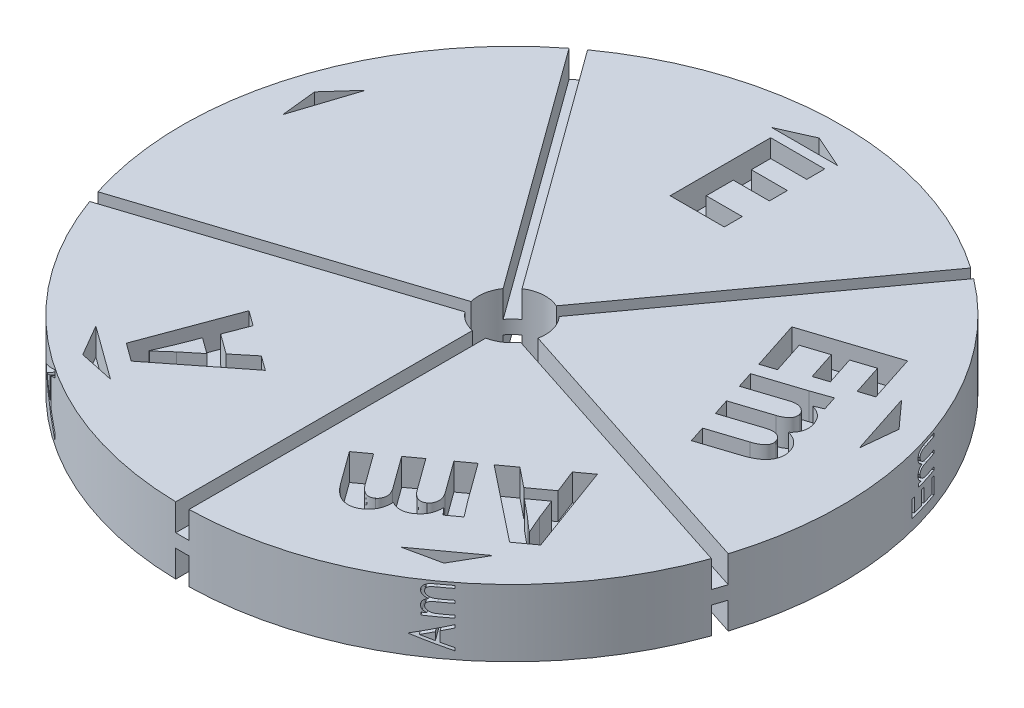
SolidWorks part; units mm, degrees
ref_plane "Front Plane" through (0, 0, 0) normal (0, 0, 1) x (1, 0, 0)
ref_plane "Top Plane" through (0, 0, 0) normal (0, 1, 0) x (1, 0, 0)
ref_plane "Right Plane" through (0, 0, 0) normal (1, 0, 0) x (0, 0, -1)
sketch "Sketch2" plane through (0, 0, 0) normal (0, 1, 0) x (1, 0, 0)
  circle A0 centre (0, 0) radius 3.175
  circle A1 centre (0, 0) radius 31.242
  dimension "D1" = 6.35
  dimension "D2" = 62.484
extrude "Boss-Extrude1" add sketch "Sketch2" along normal blind 6.35
sketch "Sketch3" plane through (0, 6.35, 0) normal (0, 1, 0) x (1, 0, 0)
  line L0 (0, 0) -> (0, 29.1218) construction
  line L1 (-8.7599, 17.3214) -> (8.7599, 17.3214) construction
  line L2 (0, 0) -> (27.6965, 8.9991) construction
  line L3 (13.7666, 13.6838) -> (19.1806, -2.9786) construction
  line L4 (0, 0) -> (17.1174, -23.56) construction
  line L5 (17.2682, -8.8643) -> (3.0943, -19.1622) construction
  line L6 (0, 0) -> (-17.1174, -23.56) construction
  line L7 (-3.0943, -19.1622) -> (-17.2682, -8.8643) construction
  line L8 (0, 0) -> (-27.6965, 8.9991) construction
  line L9 (-19.1806, -2.9786) -> (-13.7666, 13.6838) construction
  line L10 (-2.3202, 26.8464) -> (2.8087, 26.8464)
  line L11 (2.8087, 26.8464) -> (2.8087, 25.1368)
  line L12 (2.8087, 25.1368) -> (-0.6106, 25.1368)
  line L13 (-0.6106, 25.1368) -> (-0.6106, 23.305)
  line L14 (-0.6106, 23.305) -> (2.8087, 23.305)
  line L15 (2.8087, 23.305) -> (2.8087, 21.5954)
  line L16 (2.8087, 21.5954) -> (-0.6106, 21.5954)
  line L17 (-0.6106, 21.5954) -> (-0.6106, 19.031)
  line L18 (-0.6106, 19.031) -> (2.8087, 19.031)
  line L19 (2.8087, 19.031) -> (2.8087, 17.3214)
  line L20 (2.8087, 17.3214) -> (-2.3202, 17.3214)
  line L21 (-2.3202, 17.3214) -> (-2.3202, 26.8464)
  line L22 (16.0616, 11.1654) -> (18.3666, 11.9144)
  line L23 (18.3666, 11.9144) -> (19.2451, 9.2109)
  line L24 (19.2451, 9.2109) -> (20.5484, 9.6345)
  line L25 (20.5484, 9.6345) -> (19.6699, 12.338)
  line L26 (19.6699, 12.338) -> (21.6733, 12.989)
  line L27 (21.6733, 12.989) -> (22.6043, 10.1239)
  line L28 (22.6043, 10.1239) -> (23.9399, 10.5579)
  line L29 (23.9399, 10.5579) -> (22.4909, 15.0171)
  line L30 (22.4909, 15.0171) -> (14.208, 12.3255)
  line L31 (14.208, 12.3255) -> (15.7131, 7.694)
  line L32 (15.7131, 7.694) -> (17.0487, 8.128)
  line L33 (17.0487, 8.128) -> (16.0616, 11.1654)
  line L34 (21.7445, 6.7907) -> (21.7354, 6.8239)
  line L35 (21.7354, 6.8239) -> (22.5079, 7.1583)
  line L36 (22.5079, 7.1583) -> (22.0669, 8.5154)
  line L37 (20.281, 7.887) -> (16.0923, 6.5262)
  line L38 (16.0923, 6.5262) -> (16.5998, 4.9645)
  line L39 (16.5998, 4.9645) -> (20.2081, 6.137)
  line L40 (20.7301, 4.3062) -> (17.1878, 3.1549)
  line L41 (17.1878, 3.1549) -> (17.6954, 1.5932)
  line L42 (17.6954, 1.5932) -> (21.3359, 2.7762)
  line L43 (21.6757, 0.8859) -> (18.2834, -0.2164)
  line L44 (18.2834, -0.2164) -> (18.7909, -1.7781)
  line L45 (18.7909, -1.7781) -> (22.4315, -0.5951)
  line L46 (22.7262, 3.513) -> (22.7206, 3.5358)
  line L47 (20.2153, -17.4878) -> (17.0941, -8.9908)
  line L48 (17.0941, -8.9908) -> (15.7197, -9.9892)
  line L49 (15.7197, -9.9892) -> (16.5853, -12.202)
  line L50 (16.5853, -12.202) -> (14.6978, -13.5732)
  line L51 (14.6978, -13.5732) -> (12.8427, -12.0793)
  line L52 (12.8427, -12.0793) -> (11.4225, -13.111)
  line L53 (11.4225, -13.111) -> (18.5111, -18.7259)
  line L54 (18.5111, -18.7259) -> (20.2153, -17.4878)
  line L55 (18.6137, -16.9438) -> (18.5878, -16.9624)
  line L56 (17.2206, -15.7573) -> (15.6357, -14.4596)
  line L57 (15.6357, -14.4596) -> (17.1384, -13.368)
  line L58 (17.1384, -13.368) -> (17.8884, -15.2868)
  line L59 (12.5435, -19.0457) -> (12.5711, -19.0241)
  line L60 (12.5711, -19.0241) -> (13.1278, -19.6555)
  line L61 (13.1278, -19.6555) -> (14.2822, -18.8169)
  line L62 (13.1334, -17.3134) -> (10.5447, -13.7491)
  line L63 (10.5447, -13.7491) -> (9.2162, -14.7143)
  line L64 (9.2162, -14.7143) -> (11.446, -17.7837)
  line L65 (9.8656, -18.8474) -> (7.6769, -15.8325)
  line L66 (7.6769, -15.8325) -> (6.3483, -16.7977)
  line L67 (6.3483, -16.7977) -> (8.5981, -19.8946)
  line L68 (6.9042, -20.8025) -> (4.809, -17.9159)
  line L69 (4.809, -17.9159) -> (3.4805, -18.8811)
  line L70 (3.4805, -18.8811) -> (5.7303, -21.978)
  line L71 (9.7296, -20.991) -> (9.7482, -20.9768)
  line L72 (-14.2878, -21.7947) -> (-7.1717, -16.1998)
  line L73 (-7.1717, -16.1998) -> (-8.5461, -15.2014)
  line L74 (-8.5461, -15.2014) -> (-10.3829, -16.7086)
  line L75 (-10.3829, -16.7086) -> (-12.2704, -15.3374)
  line L76 (-12.2704, -15.3374) -> (-11.4231, -13.1114)
  line L77 (-11.4231, -13.1114) -> (-12.8433, -12.0796)
  line L78 (-12.8433, -12.0796) -> (-15.992, -20.5567)
  line L79 (-15.992, -20.5567) -> (-14.2878, -21.7947)
  line L80 (-14.2643, -20.1055) -> (-14.2912, -20.0845)
  line L81 (-13.5678, -18.4142) -> (-12.8235, -16.5034)
  line L82 (-12.8235, -16.5034) -> (-11.3208, -17.595)
  line L83 (-11.3208, -17.595) -> (-12.9138, -18.9014)
  line L84 (0, 29.1218) -> (-3.1045, 27.7361)
  line L85 (-3.1045, 27.7361) -> (3.1356, 27.7361)
  line L86 (3.1356, 27.7361) -> (0, 29.1218)
  line L87 (27.3475, 5.5888) -> (27.6965, 8.9991)
  line L88 (27.6965, 8.9991) -> (25.4192, 11.5235)
  line L89 (25.4192, 11.5235) -> (27.3475, 5.5888)
  line L90 (13.7661, -24.282) -> (17.1174, -23.56)
  line L91 (17.1174, -23.56) -> (18.8144, -20.6142)
  line L92 (18.8144, -20.6142) -> (13.7661, -24.282)
  line L93 (-18.8396, -20.5959) -> (-17.1174, -23.56)
  line L94 (-17.1174, -23.56) -> (-13.7913, -24.2637)
  line L95 (-13.7913, -24.2637) -> (-18.8396, -20.5959)
  line L96 (-25.4096, 11.553) -> (-27.6965, 8.9991)
  line L97 (-27.6965, 8.9991) -> (-27.3379, 5.6184)
  line L98 (-27.3379, 5.6184) -> (-25.4096, 11.553)
  spline S0 degree 3 poles (22.7206, 3.5358) (22.8505, 3.6417) (23.0222, 3.8266) (23.1833, 4.118) (23.2684, 4.3513) (23.3184, 4.5982) (23.3302, 4.9503) (23.2814, 5.2159) (23.2244, 5.3894) knots 0 0 0 0 0.245811 0.364788 0.485858 0.608329 0.732518 1 1 1 1
  spline S1 degree 3 poles (23.2244, 5.3894) (23.1882, 5.4952) (23.1257, 5.6475) (23.0256, 5.8372) (22.9463, 5.9655) (22.8634, 6.0844) (22.7724, 6.1913) (22.6762, 6.2882) (22.541, 6.4001) (22.3695, 6.5199) (22.0997, 6.676) (21.8871, 6.7566) (21.7445, 6.7907) knots 0 0 0 0 0.157381 0.231376 0.301838 0.36972 0.435229 0.499423 0.561679 0.682063 0.793713 1 1 1 1
  spline S2 degree 3 poles (22.0669, 8.5154) (21.7931, 8.4111) (21.2006, 8.1934) (20.6013, 7.9954) (20.281, 7.887) knots 0 0 0 0 0.464326 1 1 1 1
  spline S3 degree 3 poles (20.2081, 6.137) (20.3036, 6.1674) (20.4466, 6.1961) (20.6345, 6.221) (20.7652, 6.2239) (20.8891, 6.2159) (21.0065, 6.197) (21.1165, 6.1633) (21.2521, 6.1075) (21.4015, 6.0192) (21.5986, 5.8518) (21.6993, 5.6897) (21.7363, 5.573) knots 0 0 0 0 0.166013 0.241835 0.314414 0.382587 0.447893 0.511309 0.573122 0.691026 0.797762 1 1 1 1
  spline S4 degree 3 poles (21.7363, 5.573) (21.7588, 5.5001) (21.7791, 5.39) (21.7797, 5.2448) (21.7665, 5.1439) (21.7406, 5.0474) (21.6981, 4.9566) (21.6447, 4.8693) (21.5516, 4.7608) (21.4115, 4.6366) (21.1364, 4.4559) (20.8985, 4.359) (20.7301, 4.3062) knots 0 0 0 0 0.125369 0.182881 0.238167 0.292234 0.346525 0.40263 0.460044 0.580943 0.709299 1 1 1 1
  spline S5 degree 3 poles (21.3359, 2.7762) (21.4338, 2.8056) (21.5788, 2.839) (21.7692, 2.8622) (21.8992, 2.8676) (22.0215, 2.8611) (22.1362, 2.8442) (22.2428, 2.8122) (22.3706, 2.7565) (22.5111, 2.6681) (22.6972, 2.5004) (22.7906, 2.3386) (22.8245, 2.2232) knots 0 0 0 0 0.172621 0.25067 0.323611 0.391985 0.457362 0.518958 0.57929 0.692443 0.797579 1 1 1 1
  spline S6 degree 3 poles (22.8245, 2.2232) (22.8489, 2.1496) (22.8691, 2.0375) (22.8692, 1.8896) (22.8574, 1.7859) (22.8265, 1.6872) (22.7814, 1.5936) (22.7247, 1.5026) (22.6233, 1.3885) (22.4679, 1.2542) (22.1484, 1.0567) (21.8728, 0.9476) (21.6757, 0.8859) knots 0 0 0 0 0.116847 0.170441 0.222804 0.273664 0.325668 0.37942 0.434958 0.555338 0.688012 1 1 1 1
  spline S7 degree 3 poles (22.4315, -0.5951) (22.6323, -0.5281) (22.9188, -0.4156) (23.2713, -0.2345) (23.5001, -0.0953) (23.7028, 0.0516) (23.8785, 0.2083) (24.0275, 0.3736) (24.1469, 0.5493) (24.2448, 0.7281) (24.3179, 0.9113) (24.3741, 1.0962) (24.4048, 1.2846) (24.4128, 1.476) (24.3948, 1.7381) (24.3485, 1.9332) (24.306, 2.0609) knots 0 0 0 0 0.172996 0.250842 0.323557 0.391577 0.455104 0.515479 0.57292 0.628236 0.681691 0.7338 0.78582 0.837193 0.889977 1 1 1 1
  spline S8 degree 3 poles (24.306, 2.0609) (24.2557, 2.2271) (24.1477, 2.4653) (23.9488, 2.7505) (23.7718, 2.9472) (23.5635, 3.1273) (23.2218, 3.3391) (22.9309, 3.452) (22.7262, 3.513) knots 0 0 0 0 0.232076 0.347038 0.464001 0.585292 0.714053 1 1 1 1
  spline S9 degree 3 poles (17.8884, -15.2868) (18.0011, -15.5624) (18.2399, -16.1162) (18.4911, -16.6643) (18.6137, -16.9438) knots 0 0 0 0 0.49388 1 1 1 1
  spline S10 degree 3 poles (18.5878, -16.9624) (18.3622, -16.7622) (17.9127, -16.3536) (17.455, -15.954) (17.2206, -15.7573) knots 0 0 0 0 0.496404 1 1 1 1
  spline S11 degree 3 poles (9.7482, -20.9768) (9.8886, -21.0686) (10.1174, -21.1765) (10.4448, -21.2379) (10.6928, -21.2483) (10.9437, -21.2189) (11.2822, -21.1195) (11.5204, -20.9918) (11.6683, -20.8845) knots 0 0 0 0 0.24583 0.364726 0.485588 0.608004 0.732803 1 1 1 1
  spline S12 degree 3 poles (11.6683, -20.8845) (11.8377, -20.7545) (12.0656, -20.5421) (12.2943, -20.2136) (12.4047, -19.966) (12.478, -19.722) (12.5444, -19.418) (12.5535, -19.191) (12.5435, -19.0457) knots 0 0 0 0 0.301372 0.43559 0.561794 0.681954 0.794542 1 1 1 1
  spline S13 degree 3 poles (14.2822, -18.8169) (14.0951, -18.5915) (13.7154, -18.0878) (13.3307, -17.5879) (13.1334, -17.3134) knots 0 0 0 0 0.464235 1 1 1 1
  spline S14 degree 3 poles (11.446, -17.7837) (11.503, -17.8662) (11.5759, -17.9928) (11.6561, -18.1645) (11.7011, -18.2871) (11.7301, -18.4083) (11.7496, -18.526) (11.752, -18.6416) (11.7417, -18.7874) (11.7033, -18.9566) (11.6054, -19.1958) (11.4808, -19.3413) (11.3815, -19.4128) knots 0 0 0 0 0.166107 0.241932 0.314167 0.382302 0.448306 0.511767 0.573556 0.690523 0.797736 1 1 1 1
  spline S15 degree 3 poles (11.3815, -19.4128) (11.3184, -19.4546) (11.2213, -19.5103) (11.0839, -19.5555) (10.9835, -19.5744) (10.8836, -19.577) (10.7842, -19.5678) (10.6856, -19.5422) (10.5537, -19.4882) (10.3911, -19.3937) (10.1346, -19.1868) (9.9679, -18.9914) (9.8656, -18.8474) knots 0 0 0 0 0.124852 0.18256 0.237396 0.292261 0.346467 0.401192 0.459284 0.580485 0.709085 1 1 1 1
  spline S16 degree 3 poles (8.5981, -19.8946) (8.6546, -19.9799) (8.7351, -20.106) (8.8132, -20.2815) (8.8612, -20.4032) (8.8919, -20.5221) (8.9088, -20.637) (8.9125, -20.7476) (8.8993, -20.8866) (8.8575, -21.0472) (8.7573, -21.2769) (8.6304, -21.4147) (8.5316, -21.4827) knots 0 0 0 0 0.173023 0.250976 0.323896 0.393417 0.457675 0.519452 0.579613 0.692719 0.797903 1 1 1 1
  spline S17 degree 3 poles (8.5316, -21.4827) (8.4687, -21.5279) (8.369, -21.583) (8.2285, -21.629) (8.1254, -21.6473) (8.022, -21.6512) (7.9184, -21.6369) (7.8151, -21.6094) (7.6752, -21.549) (7.4999, -21.4419) (7.213, -21.1996) (7.0255, -20.9695) (6.9042, -20.8025) knots 0 0 0 0 0.116791 0.170488 0.222389 0.274344 0.325871 0.379656 0.435071 0.555226 0.688094 1 1 1 1
  spline S18 degree 3 poles (5.7303, -21.978) (5.8566, -22.148) (6.0505, -22.3875) (6.3319, -22.6674) (6.5353, -22.8421) (6.7381, -22.9891) (6.9419, -23.1069) (7.1446, -23.1984) (7.3484, -23.2592) (7.5491, -23.2948) (7.7464, -23.3109) (7.9392, -23.3015) (8.1282, -23.2748) (8.3122, -23.2222) (8.5579, -23.1279) (8.7282, -23.021) (8.8364, -22.9412) knots 0 0 0 0 0.173047 0.250946 0.323703 0.391779 0.455121 0.515622 0.572909 0.6282 0.681871 0.734101 0.785508 0.837339 0.890015 1 1 1 1
  spline S19 degree 3 poles (8.8364, -22.9412) (8.9761, -22.84) (9.1722, -22.6672) (9.3808, -22.389) (9.5128, -22.1593) (9.6201, -21.906) (9.7182, -21.5163) (9.7356, -21.2047) (9.7296, -20.991) knots 0 0 0 0 0.231288 0.346683 0.463963 0.585241 0.713654 1 1 1 1
  spline S20 degree 3 poles (-12.9138, -18.9014) (-13.1404, -19.0949) (-13.5927, -19.494) (-14.0388, -19.8999) (-14.2643, -20.1055) knots 0 0 0 0 0.494052 1 1 1 1
  spline S21 degree 3 poles (-14.2912, -20.0845) (-14.17, -19.8087) (-13.92, -19.2558) (-13.6835, -18.6969) (-13.5678, -18.4142) knots 0 0 0 0 0.496504 1 1 1 1
  point P9 (0, 17.3214)
  point P24 (0, 0)
  point P316 (0, 0)
  dimension "D1" = 5
  dimension "D2" = 5
sketch "Sketch4" plane through (0, 6.35, 0) normal (0, 1, 0) x (1, 0, 0)
  line L1 (-0.5082, 0.3692) -> (17.9061, 25.7142)
  line L2 (0.4656, 0.2237) -> (30.2605, -9.4573)
  line L3 (-0.5082, 0.3692) -> (0.5082, -0.3692)
  line L4 (17.9061, 25.7142) -> (18.9224, 24.9758)
  line L5 (0.5082, -0.3692) -> (18.9224, 24.9758)
  line L6 (6.2078, 9.613) -> (7.2242, 8.8746)
  line L7 (0, 0) -> (27.6965, 8.9991) construction
  line L8 (6.716, 9.2438) -> (0, 0) construction
  line L9 (0, 0) -> (0, 29.1218) construction
  line L10 (0.4656, 0.2237) -> (0.0774, -0.9711)
  line L11 (0.0774, -0.9711) -> (29.8723, -10.652)
  line L12 (30.2605, -9.4573) -> (29.8723, -10.652)
  line L13 (0.6281, -0.7474) -> (0.6281, -32.0756)
  line L14 (0.6281, -0.7474) -> (-0.6281, -0.7474)
  line L15 (-0.6281, -0.7474) -> (-0.6281, -32.0756)
  line L16 (0.6281, -32.0756) -> (-0.6281, -32.0756)
  line L17 (-0.2452, -1.2021) -> (-30.0401, -10.883)
  line L18 (-0.2452, -1.2021) -> (-0.6334, -0.0073)
  line L19 (-0.6334, -0.0073) -> (-30.4283, -9.6882)
  line L20 (-30.0401, -10.883) -> (-30.4283, -9.6882)
  line L21 (-0.9475, -0.512) -> (-19.3617, 24.8331)
  line L22 (-0.9475, -0.512) -> (0.0688, 0.2265)
  line L23 (0.0688, 0.2265) -> (-18.3454, 25.5715)
  line L24 (-19.3617, 24.8331) -> (-18.3454, 25.5715)
  point P13 (6.716, 9.2438)
  point P36 (-0.1214, -0.3737)
  circle M10 centre (0, 0) radius 3.175
  dimension "D1" = 5
  dimension "D3" = 36
  dimension "D4" = 36
extrude "Cut-Extrude2" cut sketch "Sketch4" against normal blind 2.54 contours L20 L17 L19 M10 | L16 L13 L15 M10 | L12 L2 L11 M10 | L24 L21 L23 M10 | L8 L6 L1 M10 | L1 L6 L5 L4 | L6 L8 L5 M10 region at (4.0306, 6.35, -6.0826) region at (12.5651, 6.35, -17.2944) region at (4.5394, 6.35, -5.7129) region at (-10.5228, 6.35, -13.7349) region at (-16.534, 6.35, 5.8348) region at (16.4853, 6.35, 5.6423) region at (0, 6.35, 17.6149)
extrude "Cut-Extrude3" cut sketch "Sketch3" against normal blind 2.54
ref_plane "Plane1" through (29.7129, 6.35, -9.6543) normal (0.9511, 0, -0.309) x (-0.309, 0, -0.9511)
sketch "Sketch6" plane through (29.7129, 6.35, -9.6543) normal (0.9511, 0, -0.309) x (-0.309, 0, -0.9511)
  line L0 (1.0543, 0.0126) -> (1.0543, -6.35) construction
  text T0 "Em" font "Century Gothic" height 3.175
extrude "Cut-Extrude5" cut sketch "Sketch6" against normal blind 2.54
ref_plane "Plane2" through (18.3636, 6.35, 25.2753) normal (0.5878, 0, 0.809) x (0.809, 0, -0.5878)
sketch "Sketch7" plane through (18.3636, 6.35, 25.2753) normal (0.5878, 0, 0.809) x (0.809, 0, -0.5878)
  line L0 (1.0968, -0.0015) -> (1.0968, -6.35) construction
  text T0 "Am" font "Century Gothic" height 3.175
extrude "Cut-Extrude6" cut sketch "Sketch7" against normal blind 2.54
ref_plane "Plane3" through (-18.3636, 6.35, 25.2753) normal (-0.5878, 0, 0.809) x (0.809, 0, 0.5878)
sketch "Sketch8" plane through (-18.3636, 6.35, 25.2753) normal (-0.5878, 0, 0.809) x (0.809, 0, 0.5878)
  line L0 (1.2625, 0) -> (1.2625, -6.35) construction
  text T0 "A" font "Century Gothic" height in points 18
extrude "Cut-Extrude7" cut sketch "Sketch8" against normal blind 2.54
ref_plane "Plane4" through (0, 6.35, -31.242) normal (0, 0, -1) x (-1, 0, 0)
sketch "Sketch9" plane through (0, 6.35, -31.242) normal (0, 0, -1) x (-1, 0, 0)
  line L0 (3.5738, -1.1666) -> (3.5738, -7.0477) construction
  text T0 "E" font "Century Gothic" height in points 22
extrude "Cut-Extrude8" cut sketch "Sketch9" against normal blind 2.54
ref_plane "Plane5" through (0, 3.175, 0) normal (0, 1, 0) x (1, 0, 0)
mirror "Mirror4" about plane through (0, 3.175, 0) normal (0, 1, 0) of "Cut-Extrude2"
